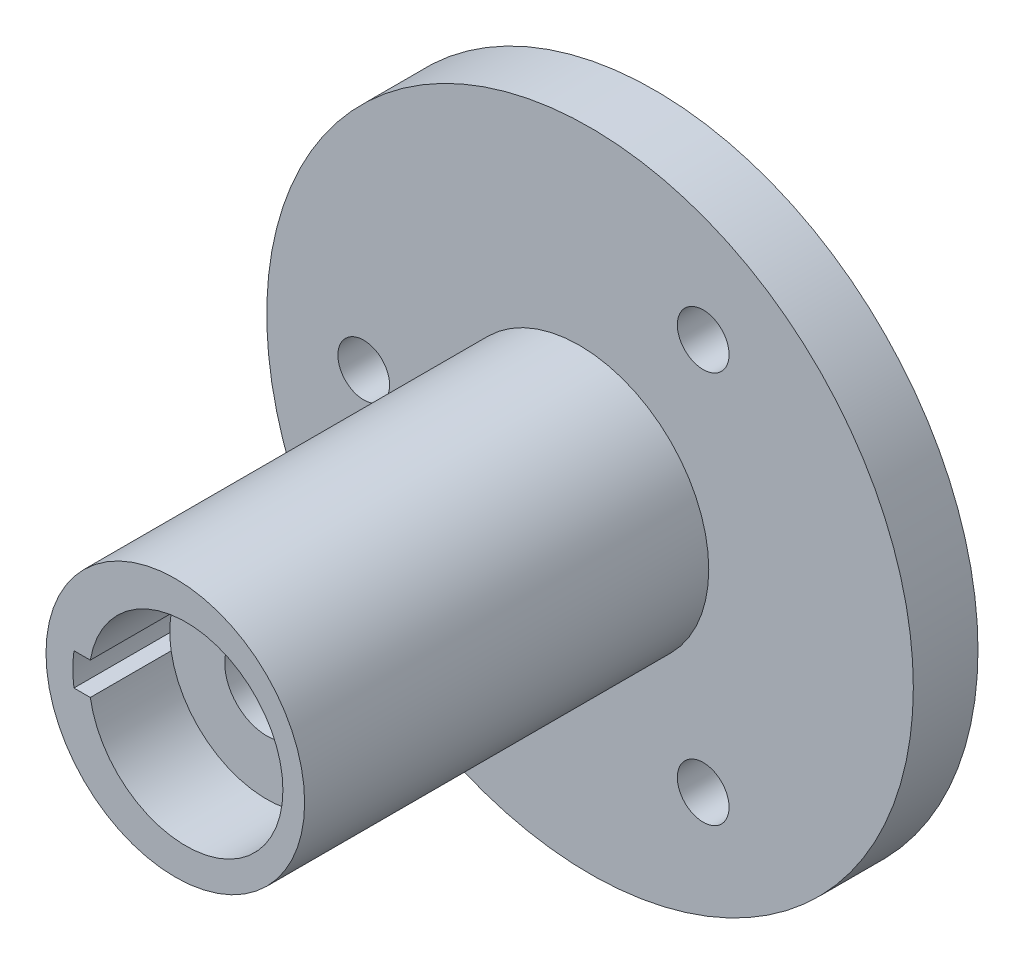
SolidWorks part; units mm, degrees
ref_plane "Front Plane" through (0, 0, 0) normal (0, 0, 1) x (1, 0, 0)
ref_plane "Top Plane" through (0, 0, 0) normal (0, 1, 0) x (1, 0, 0)
ref_plane "Right Plane" through (0, 0, 0) normal (1, 0, 0) x (0, 0, -1)
sketch "Sketch1" plane through (0, 0, 0) normal (0, 0, 1) x (1, 0, 0)
  line L0 (0, 0) -> (-58.2991, 0) construction
  line L1 (-14.7902, 2.5) -> (-17.3205, 2.5)
  line L2 (-14.7902, -2.5) -> (-17.3205, -2.5)
  circle A0 centre (0, 0) radius 50
  arc A1 (-14.7902, -2.5) -> (-14.7902, 2.5) centre (0, 0) ccw
  arc A2 (-17.3205, 2.5) -> (-17.3205, -2.5) centre (0, 0) ccw
  circle A3 centre (0, 0) radius 17.5 construction
  circle A4 centre (0, 0) radius 15 construction
  circle A5 centre (0, 0) radius 35
  circle A6 centre (-35, 0) radius 4
  circle A7 centre (17.5, 30.3109) radius 4
  circle A8 centre (17.5, -30.3109) radius 4
  circle A9 centre (-1.6409, 0) radius 20
  point P20 (0, 0)
  dimension "D1" = 100
  dimension "D2" = 30
  dimension "D4" = 3
  dimension "D3" = 2.5
extrude "Boss-Extrude1" add sketch "Sketch1" against normal blind 10 contours A0
extrude "Cut-Extrude1" cut sketch "Sketch1<3>" against normal blind 10 contours A6 | A7 | A8
sketch "Sketch1<3>" plane through (0, 0, 0) normal (0, 0, 1) x (1, 0, 0) same geometry as "Sketch1"
extrude "Boss-Extrude2" add sketch "Sketch1<4>" along normal blind 62.5 contours A9 A2 L1 A1 L2 region at (-21.0752, 0, 0)
sketch "Sketch1<4>" plane through (0, 0, 0) normal (0, 0, 1) x (1, 0, 0) same geometry as "Sketch1"
sketch "Sketch3" plane through (0, 0, 0) normal (0, 0, 1) x (1, 0, 0)
  circle A0 centre (0, 0) radius 6.5
sketch "Sketch4" plane through (0, 0, 0) normal (0, 0, 1) x (1, 0, 0)
  circle A0 centre (0, 0) radius 15
extrude "Boss-Extrude4" add sketch "Sketch4" along normal blind 50 contours A0
extrude "Cut-Extrude3" cut sketch "Sketch3" against normal through all both and the other way through all contours A0
sketch "Sketch5" plane through (0, 0, 0) normal (0, 0, 1) x (1, 0, 0)
  line L0 (0, 0) -> (-50, 0) construction
  circle A0 centre (0, 0) radius 50 construction
